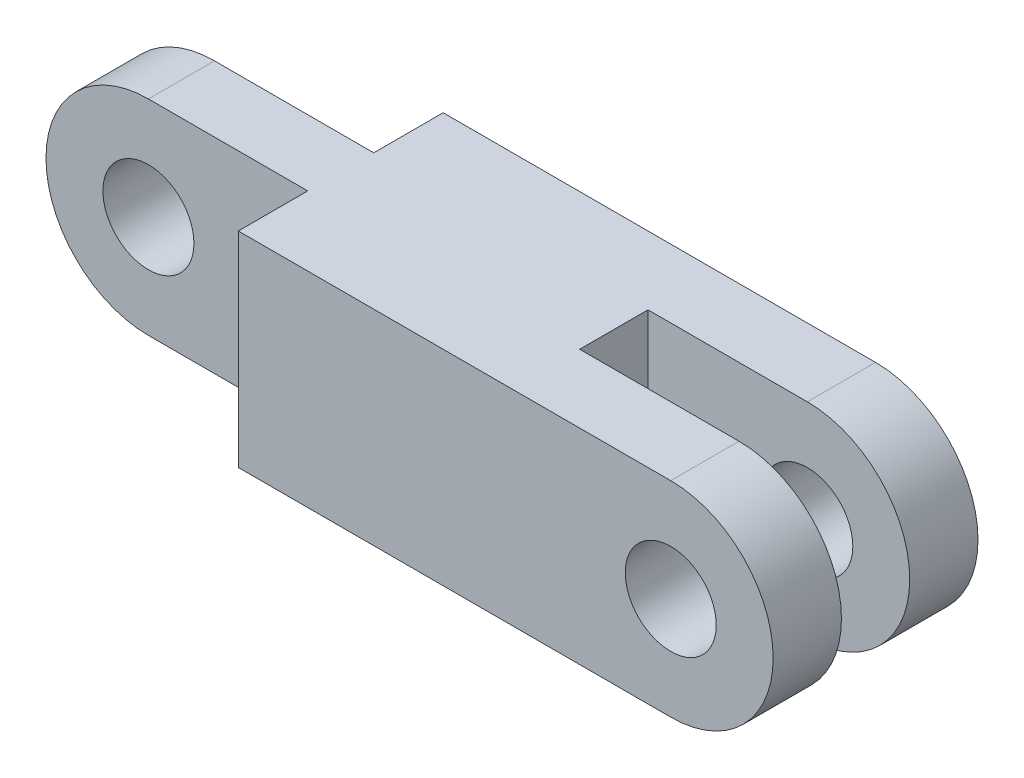
SolidWorks part; units mm, degrees
ref_plane "Front Plane" through (0, 0, 0) normal (0, 0, 1) x (1, 0, 0)
ref_plane "Top Plane" through (0, 0, 0) normal (0, 1, 0) x (1, 0, 0)
ref_plane "Right Plane" through (0, 0, 0) normal (1, 0, 0) x (0, 0, -1)
sketch "Sketch1" plane through (0, 0, 0) normal (0, 0, 1) x (1, 0, 0)
  line L0 (0, 22.5) -> (0, -22.5)
  line L1 (0, -22.5) -> (-35, -22.5)
  line L2 (0, 22.5) -> (-35, 22.5)
  arc A0 (-35, 22.5) -> (-35, -22.5) centre (-35, 0) ccw
  circle A1 centre (-35, 0) radius 10
  point P6 (0, 0)
  dimension "D3" = 22.5
  dimension "D4" = 20
  dimension "D1" = 45
  dimension "D2" = 35
extrude "Boss-Extrude1" add sketch "Sketch1" along normal blind 7.25 and the other way blind 7.25
sketch "Sketch2" plane through (0, 0, 0) normal (1, 0, 0) x (0, 0, -1)
  line L1 (-22.5, -22.5) -> (22.5, -22.5)
  line L2 (-22.5, -22.5) -> (-22.5, 22.5)
  line L3 (-22.5, 22.5) -> (22.5, 22.5)
  line L4 (22.5, -22.5) -> (22.5, 22.5)
  line L5 (-22.5, -22.5) -> (22.5, 22.5) construction
  line L6 (-22.5, 22.5) -> (22.5, -22.5) construction
  line L7 (7.25, -22.5) -> (-7.25, -22.5) construction
  point P0 (0, 0)
  point P8 (0, -22.5)
  dimension "D1" = 45
extrude "Boss-Extrude2" add sketch "Sketch2" along normal blind 60
ref_plane "Plane1" through (0, 0, 7.5) normal (0, 0, 1) x (1, 0, 0)
sketch "Sketch3" plane through (0, 0, 7.5) normal (0, 0, 1) x (1, 0, 0)
  line L0 (60, 22.5) -> (60, -22.5)
  line L1 (60, -22.5) -> (95, -22.5)
  line L3 (95, 22.5) -> (60, 22.5)
  arc A0 (95, 22.5) -> (95, -22.5) centre (95, 0) cw
  circle A1 centre (95, 0) radius 10
  dimension "D3" = 20
  dimension "D4" = 22.5
  dimension "D1" = 45
  dimension "D2" = 35
extrude "Boss-Extrude3" add sketch "Sketch3" along normal blind 15
mirror "Mirror1" about plane through (0, 0, 0) normal (0, 0, 1) of "Boss-Extrude3"
